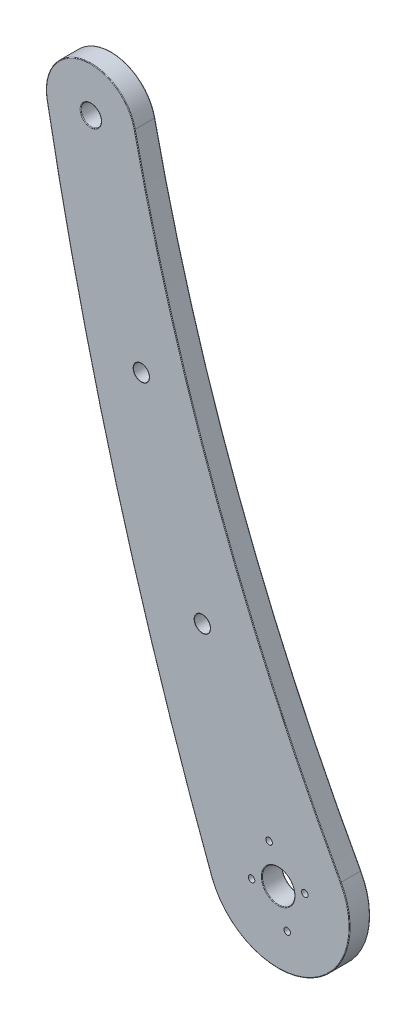
SolidWorks part; units mm, degrees
ref_plane "Front Plane" through (0, 0, 0) normal (0, 0, 1) x (1, 0, 0)
ref_plane "Top Plane" through (0, 0, 0) normal (0, 1, 0) x (1, 0, 0)
ref_plane "Right Plane" through (0, 0, 0) normal (1, 0, 0) x (0, 0, -1)
sketch "Sketch1" plane through (0, 0, 0) normal (0, 0, 1) x (1, 0, 0)
  line L0 (-20.22, 57.58) -> (-66.1462, 198.2739) construction
  line L1 (-20.22, 57.58) -> (-66.1462, 198.2739) construction
  circle A0 centre (-66.1462, 198.2739) radius 11 construction
  circle A1 centre (-66.1462, 198.2739) radius 11 construction
  circle A2 centre (-20.22, 57.58) radius 17.5 construction
  circle A3 centre (-20.22, 57.58) radius 17.5 construction
  circle A4 centre (-66.1462, 198.2739) radius 2.5
  circle A5 centre (-20.22, 57.58) radius 4
  arc A8 (-55.3989, 200.6179) -> (-4.8897, 66.02) centre (433.1175, 307.1623) ccw
  arc A9 (-76.9622, 196.2701) -> (-36.5961, 51.4097) centre (758.8158, 351.1094) ccw
  arc A10 (-66.1462, 198.2739) -> (-20.22, 57.58) centre (666.3139, 359.5257) ccw construction
  arc A11 (-76.9622, 196.2701) -> (-55.3989, 200.6179) centre (-66.1462, 198.2739) cw
  arc A12 (-4.8897, 66.02) -> (-36.5961, 51.4097) centre (-20.22, 57.58) cw
  point P15 (-53.7744, 149.8287)
  point P16 (-38.8129, 103.9945)
  dimension "D1" = 5
  dimension "D2" = 8
  dimension "D3" = 850
  dimension "D4" = 500
  dimension "D5" = 750
  dimension "D6" = 50
  dimension "D7" = 50
extrude "Boss-Extrude1" add sketch "Sketch1" against normal blind 5
sketch "Sketch4" plane through (0, 0, 0) normal (0, 0, 1) x (1, 0, 0)
  point P0 (-53.7744, 149.8287)
  point P3 (-38.8129, 103.9945)
hole_wizard "M3.5 Clearance Hole1" positions "Sketch4" profile "Sketch3" hole size "M3.5" standard "ISO"
sketch "Sketch3" plane through (-53.7744, 149.8287, 0) normal (1, 0, 0) x (0, -1, 0)
  line L0 (0, 0) -> (0, 11.1717)
  line L1 (0, 11.1717) -> (1.95, 10)
  line L2 (1.95, 10) -> (1.95, 0.025)
  line L3 (1.95, 0.025) -> (1.975, 0)
  line L5 (1.975, 0) -> (0, 0)
  line L6 (-1.95, 0.025) -> (-1.975, 0) construction
  line L10 (0, 11.1717) -> (-1.95, 10) construction
  line L11 (0, -6.35) -> (0, 107.95) construction
  dimension "Hole Dia." = 3.9
  dimension "Hole Depth" = 10
  dimension "Near C'Sink Dia." = 3.95
  dimension "Near C'Sink Angle" = 90
  dimension "Drill Angle" = 118
fillet "Fillet1" radius 0.15 16 edges at (-59.989, 122.9455, -5) (-12.8962, 41.6862, -5) (-35.0071, 131.4941, -5) (-68.3204, 209.0569, -5) (-63.6462, 198.2739, -5) (-16.22, 57.58, -5) (-40.7629, 103.9945, -5) (-55.7244, 149.8287, -5) (-35.0071, 131.4941, 0) (-12.8962, 41.6862, 0) (-59.989, 122.9455, 0) (-68.3204, 209.0569, 0) (-63.6462, 198.2739, 0) (-16.22, 57.58, 0) (-36.8379, 103.9945, 0) (-51.7994, 149.8287, 0)
sketch "Sketch6" plane through (0, 0, 0) normal (0, 0, 1) x (1, 0, 0)
  circle A0 centre (-13.6909, 59.2926) radius 0.8
  circle A1 centre (-22.4401, 66.0437) radius 0.8
  circle A2 centre (-26.7491, 55.8674) radius 0.8
  circle A3 centre (-17.9999, 49.1163) radius 0.8
  dimension "D1" = 1.6
  dimension "D2" = 1.6
  dimension "D3" = 1.6
  dimension "D4" = 1.6
  dimension "D5" = 50.0656
  dimension "D6" = 54.3746
  dimension "D7" = 58.8148
  dimension "D8" = 63.1238
  dimension "D9" = 4.4048
  dimension "D10" = 7.83
  dimension "D11" = 14.5811
  dimension "D12" = 2.3463
extrude "Cut-Extrude1" cut sketch "Sketch6" against normal through all contours A3 | A0 | A1 | A2 region at (-13.6909, 59.2926, 0) region at (-22.4401, 66.0437, 0) region at (-26.7491, 55.8674, 0) region at (-17.9999, 49.1163, 0)
